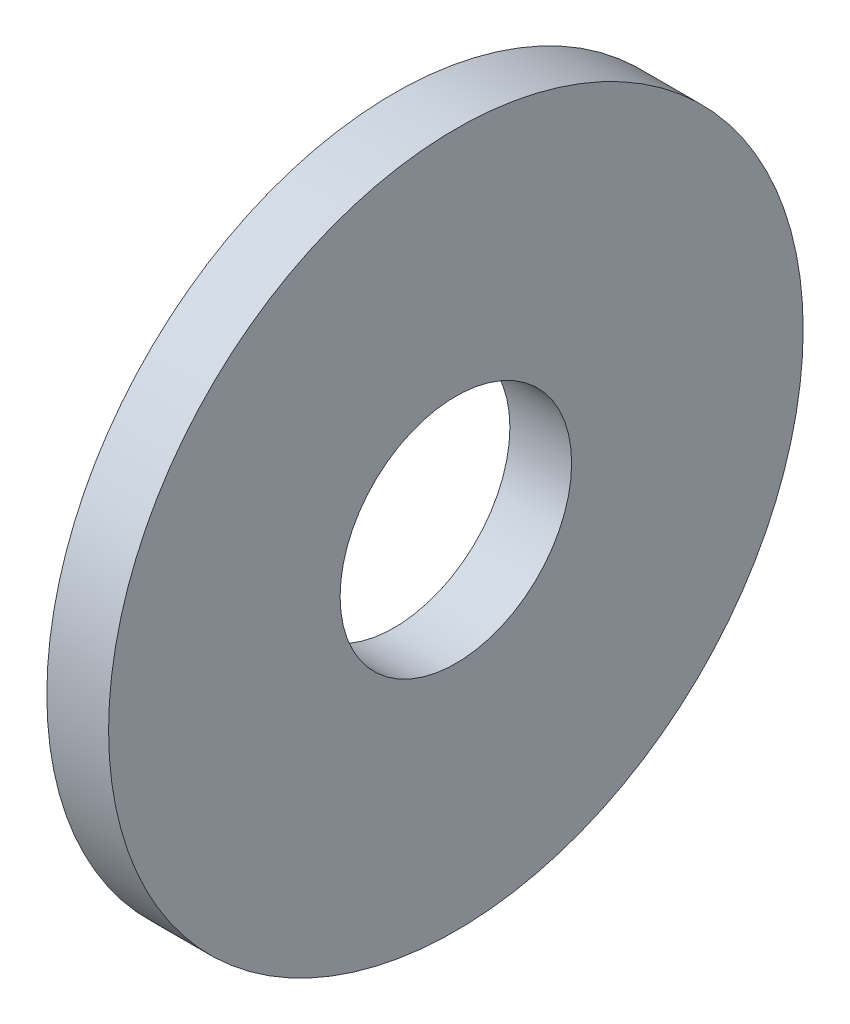
SolidWorks part; units mm, degrees
material "AISI 316 Stainless Steel Sheet (SS)"
ref_plane "前视基准面" through (0, 0, 0) normal (0, 0, 1) x (1, 0, 0)
ref_plane "上视基准面" through (0, 0, 0) normal (0, 1, 0) x (1, 0, 0)
ref_plane "右视基准面" through (0, 0, 0) normal (1, 0, 0) x (0, 0, -1)
sketch "Sketch1" plane through (0, 0, 0) normal (1, 0, 0) x (0, 0, -1)
  circle A0 centre (0, 0) radius 1.5
  circle A1 centre (0, 0) radius 4.5
  dimension "D1" = 3
  dimension "D2" = 9
extrude "Boss-Extrude1" add sketch "Sketch1" along normal blind 0.8
